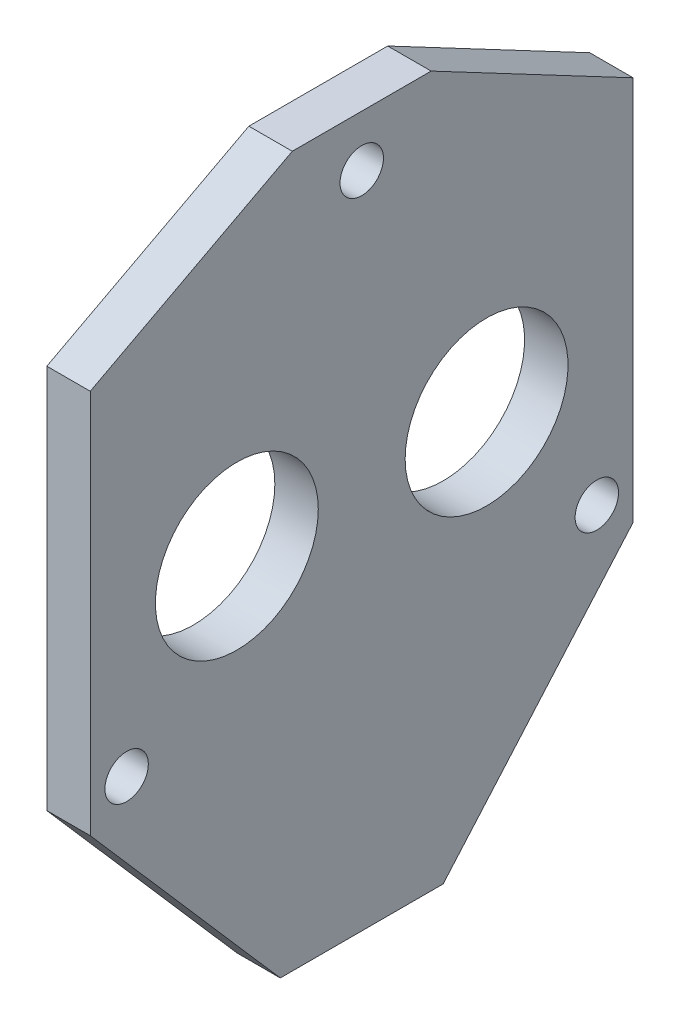
SolidWorks part; units mm, degrees
ref_plane "Front Plane" through (0, 0, 0) normal (0, 0, 1) x (1, 0, 0)
ref_plane "Top Plane" through (0, 0, 0) normal (0, 1, 0) x (1, 0, 0)
ref_plane "Right Plane" through (0, 0, 0) normal (1, 0, 0) x (0, 0, -1)
sketch "Sketch1" plane through (0, 0, 0) normal (1, 0, 0) x (0, 0, -1)
  line L0 (0, 86.3618) -> (0, -95.6447) construction
  line L1 (-89.4162, 0) -> (80.9544, 0) construction
  line L2 (12.7882, 59.481) -> (-12.7882, 59.481)
  line L3 (-12.7882, 59.481) -> (-50, 39.8029)
  line L4 (-50, 39.8029) -> (-50, -31.0898)
  line L5 (-50, -31.0898) -> (-15, -71.29)
  line L6 (-15, -71.29) -> (15, -71.29)
  line L7 (50, -31.0898) -> (15, -71.29)
  line L8 (50, 39.8029) -> (50, -31.0898)
  line L9 (12.7882, 59.481) -> (50, 39.8029)
  circle A0 centre (0, 0) radius 76.29 construction
  circle A1 centre (0, 50) radius 4
  circle A2 centre (43.3013, -25) radius 4
  circle A3 centre (-43.3013, -25) radius 4
  circle A4 centre (-23, 0) radius 15
  circle A5 centre (23, 0) radius 15
  point P14 (0, 0)
  point P16 (0, -76.29)
  point P20 (50, -29.7277)
  point P25 (0, 59.481)
  point P27 (0, -71.29)
  point P30 (0, 59.481)
  point P31 (0, 59.481)
  point P32 (0, 0)
  point P33 (50, -31.0898)
  point P34 (0, 0)
  dimension "D1" = 152.58
  dimension "D2" = 8
  dimension "D5" = 30
  dimension "D9" = 5
  dimension "D3" = 50
  dimension "D6" = 23
  dimension "D7" = 100
  dimension "D8" = 30
  dimension "D4" = 3
extrude "Boss-Extrude1" add sketch "Sketch1" along normal blind 8
